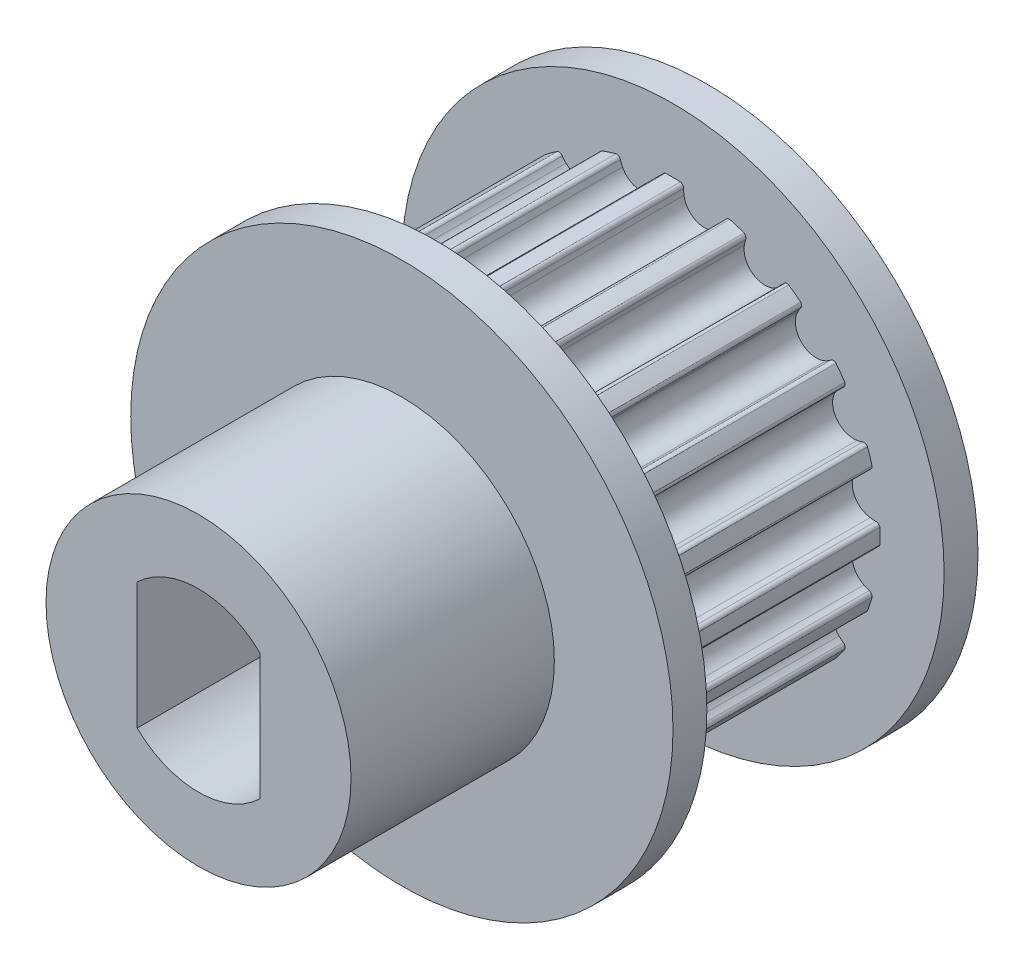
SolidWorks part; units mm, degrees
material "6063-T1"
ref_plane "Front Plane" through (0, 0, 0) normal (0, 0, 1) x (1, 0, 0)
ref_plane "Top Plane" through (0, 0, 0) normal (0, 1, 0) x (1, 0, 0)
ref_plane "Right Plane" through (0, 0, 0) normal (1, 0, 0) x (0, 0, -1)
sketch "Sketch5" plane through (0, 0, 0) normal (1, 0, 0) x (0, 0, -1)
  line L0 (0, 0) -> (0, 12.2271) construction
  line L2 (0.5, 8) -> (0.5, 6.11)
  line L3 (0.5, 6.11) -> (7.5, 6.11)
  line L4 (7.5, 6.11) -> (7.5, 8)
  line L5 (7.5, 8) -> (8.5, 8)
  line L6 (8.5, 8) -> (8.5, 2.6)
  line L8 (0, 0) -> (15.0467, 0) construction
  line L16 (-0.5, 2.6) -> (8.5, 2.6)
  line L18 (-0.5, 8) -> (0.5, 8)
  line L19 (-0.5, 8) -> (-0.5, 2.6)
  point P8 (0, 8)
  dimension "D1" = 12.22
  dimension "D2" = 7
  dimension "D3" = 9
  dimension "D4" = 1
  dimension "D5" = 16
  dimension "D6" = 5.2
revolve "Revolve1" add sketch "Sketch5" angle 360 about L8
sketch "Sketch6" plane through (0, 0, -0.5) normal (0, 0, 1) x (1, 0, 0)
  line L0 (0, 0) -> (0, 6.3662) construction
  line L1 (0, 0) -> (0.9959, 6.2878) construction
  line L2 (0, 0) -> (1.3887, 6.2129) construction
  line L3 (0, 6.1122) -> (0, 6.3662)
  line L4 (1.8888, 5.813) -> (1.9673, 6.0546)
  circle A1 centre (0, 0) radius 6.3662 construction
  arc A22 (0, 6.1122) -> (0.1975, 6.109) centre (0, 0) cw
  circle A23 centre (0, 0) radius 6.1122 construction
  circle A24 centre (0, 0) radius 5.3622 construction
  arc A25 (0.1975, 6.109) -> (0.3136, 5.9865) centre (0.1936, 5.9891) cw
  arc A26 (0.3136, 5.9865) -> (0.3242, 5.8165) centre (1.3333, 5.965) ccw
  arc A27 (0.3242, 5.8165) -> (1.4891, 5.632) centre (0.9355, 5.9064) ccw
  arc A28 (1.8888, 5.813) -> (1.7, 5.871) centre (0, 0) ccw
  arc A29 (1.5517, 5.7904) -> (1.4891, 5.632) centre (0.5752, 6.0851) cw
  arc A30 (1.7, 5.871) -> (1.5517, 5.7904) centre (1.6666, 5.7558) ccw
  arc A31 (0, 6.3662) -> (1.9673, 6.0546) centre (0, 0) cw
  dimension "D1" = 12.7324
  dimension "D6" = 0.12
  dimension "D7" = 1.02
  dimension "D8" = 0.6179
  dimension "D2" = 0.254
  dimension "D3" = 11.4744
  dimension "D4" = 9
  dimension "D5" = 3.6
extrude "Cut-Extrude1" cut sketch "Sketch6" against normal up to surface (7 mm away) up to face at (6.11, 0, -7.5)
sketch "Sketch17" plane through (0, 0, 0.5) normal (0, 0, 1) x (1, 0, 0)
  line L1 (-1.81, 2.1494) -> (-1.81, -2.1494)
  line L2 (1.81, 2.1494) -> (1.81, -2.1494)
  circle A0 centre (0, 0) radius 2.81
  circle M6 centre (0, 0) radius 2.6
  dimension "D1" = 5.62
  dimension "D2" = 3.62
extrude "Boss-Extrude1" add sketch "Sketch17" along direction (0, 0, 1) on the side against the normal up to surface (9 mm away) contours L1 M6 | L2 M6 region at (-2.1305, 0, 0.5) region at (2.1305, 0, 0.5) up to face at (8, 0, -8.5)
sketch "Sketch18" plane through (0, 0, 0.5) normal (0, 0, 1) x (1, 0, 0)
  line L6 (-1.81, 1.8665) -> (-1.81, -1.8665)
  line L7 (1.81, -1.8665) -> (1.81, 1.8665)
  line L8 (-1.81, 1.8665) -> (-1.81, -1.8665)
  line L9 (1.81, -1.8665) -> (1.81, 1.8665)
  circle A0 centre (0, 0) radius 4.5
  arc A7 (-1.81, -1.8665) -> (1.81, -1.8665) centre (0, 0) ccw
  arc A8 (1.81, 1.8665) -> (-1.81, 1.8665) centre (0, 0) ccw
  arc A9 (-1.81, -1.8665) -> (1.81, -1.8665) centre (0, 0) ccw
  arc A10 (1.81, 1.8665) -> (-1.81, 1.8665) centre (0, 0) ccw
  dimension "D1" = 0
  dimension "8" = 9
extrude "Boss-Extrude2" add sketch "Sketch18" along normal blind 6
pattern_circular "CirPattern1" count 20 over 360 about axis through (0, 0, 0) along (0, 0, 1) of "Cut-Extrude1"
sketch "Sketch19" plane through (0, 0, -8.5) normal (0, 0, -1) x (-1, 0, 0)
  line L0 (1.81, -1.8665) -> (1.81, 1.8665) construction
  line L1 (-1.81, -1.8665) -> (-1.81, 1.8665) construction
  line L2 (1.81, -1.8665) -> (1.81, 1.8665)
  line L3 (-1.81, -1.8665) -> (-1.81, 1.8665)
  arc A0 (-1.81, -1.8665) -> (1.81, -1.8665) centre (0, 0) ccw construction
  arc A1 (1.81, 1.8665) -> (-1.81, 1.8665) centre (0, 0) ccw construction
  arc A2 (-1.81, -1.8665) -> (1.81, -1.8665) centre (0, 0) ccw
  arc A3 (1.81, 1.8665) -> (-1.81, 1.8665) centre (0, 0) ccw
  circle A4 centre (0, 0) radius 4.4
  circle A5 centre (0, 0) radius 4.55
  circle A6 centre (0, 0) radius 8
  circle A7 centre (0, 0) radius 8
  circle M7 centre (0, 0) radius 8
  dimension "D2" = 8.8
  dimension "D1" = 0
  dimension "D3" = 0.15
extrude "Cut-Extrude2" cut sketch "Sketch19" against normal blind 1 contours A5 M7 | A5 A4 region at (4.4213, 0, -8.5) region at (7.7737, 0, -8.5)
extrude "Boss-Extrude3" add sketch "Sketch19<3>" against normal blind 1 separate body contours A5 M7 region at (7.7737, 0, -8.5)
sketch "Sketch19<3>" plane through (0, 0, -8.5) normal (0, 0, -1) x (-1, 0, 0) same geometry as "Sketch19"
